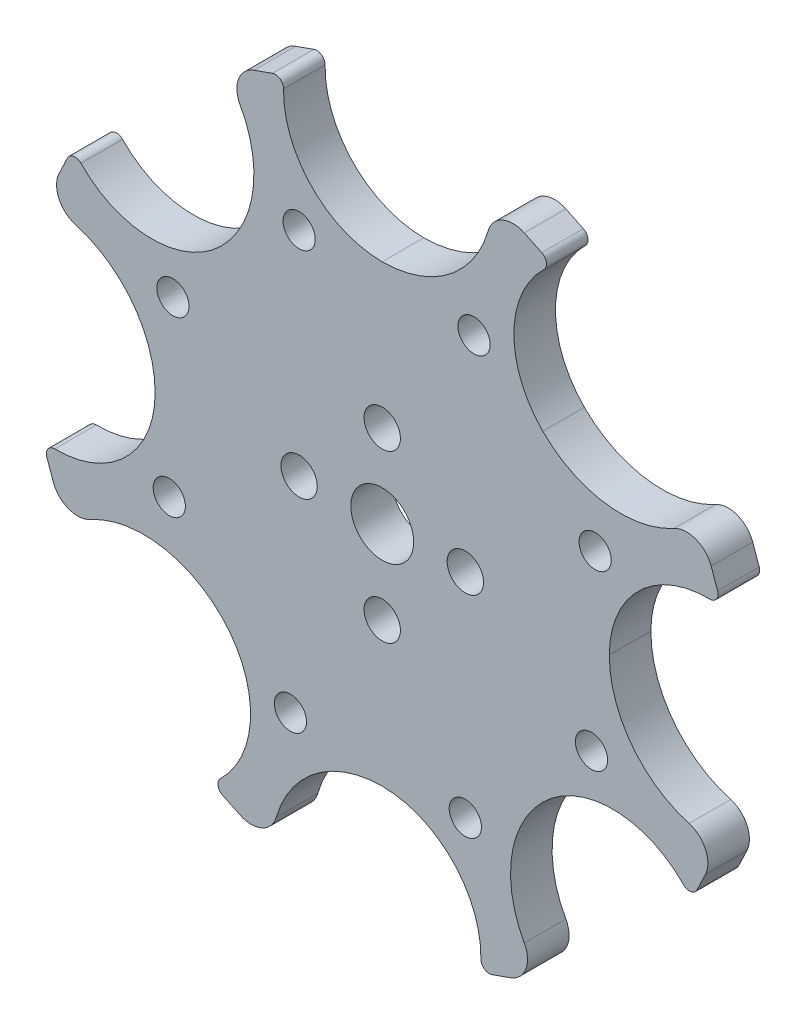
SolidWorks part; units mm, degrees
material "Thornel Mat VMA"
ref_plane "前视基准面" through (0, 0, 0) normal (0, 0, 1) x (1, 0, 0)
ref_plane "上视基准面" through (0, 0, 0) normal (0, 1, 0) x (1, 0, 0)
ref_plane "右视基准面" through (0, 0, 0) normal (1, 0, 0) x (0, 0, -1)
sketch "草图1" plane through (0, 0, 0) normal (0, 0, 1) x (1, 0, 0)
  line L0 (0, 31.3575) -> (0, 0) construction
  line L1 (0, 0) -> (22.1731, 22.1731) construction
  line L4 (0, 31.3575) -> (22.1731, 22.1731) construction
  line L6 (11.6409, 26.5357) -> (12.5976, 28.8454) construction
  line L7 (21.7656, 23.184) -> (15.5687, 29.0018) construction
  line L8 (21.7656, 23.184) -> (27.9942, 29.8184) construction
  line L9 (15.357, 30.2989) -> (13.674, 31.1018)
  line L10 (32.2836, 10.5656) -> (31.6613, 12.3233)
  line L11 (30.2989, -15.357) -> (31.1018, -13.674)
  line L12 (10.5656, -32.2836) -> (12.3233, -31.6613)
  line L13 (-15.357, -30.2989) -> (-13.674, -31.1018)
  line L14 (-32.2836, -10.5656) -> (-31.6613, -12.3233)
  line L15 (-30.2989, 15.357) -> (-31.1018, 13.674)
  line L16 (-10.5656, 32.2836) -> (-12.3233, 31.6613)
  circle A0 centre (0, 0) radius 31.3575 construction
  arc A9 (15.5687, 29.0018) -> (15.4556, 15.4556) centre (22.1731, 22.1731) ccw
  circle A13 centre (0, 0) radius 40.9 construction
  arc A16 (15.5687, 29.0018) -> (15.357, 30.2989) centre (15.0125, 29.5769) ccw
  arc A17 (13.674, 31.1018) -> (10.1948, 29.5357) centre (12.5976, 28.8454) ccw
  arc A18 (0, 21.8575) -> (10.1948, 29.5357) centre (0, 32.4647) ccw
  arc A19 (31.5161, 9.4987) -> (21.8575, 0) centre (31.3575, 0) ccw
  arc A20 (31.5161, 9.4987) -> (32.2836, 10.5656) centre (31.5295, 10.2986) ccw
  arc A21 (31.6613, 12.3233) -> (28.0937, 13.6761) centre (29.3046, 11.4889) ccw
  arc A22 (15.4556, 15.4556) -> (28.0937, 13.6761) centre (22.956, 22.956) ccw
  arc A24 (29.0018, -15.5687) -> (15.4556, -15.4556) centre (22.1731, -22.1731) ccw
  arc A25 (29.0018, -15.5687) -> (30.2989, -15.357) centre (29.5769, -15.0125) ccw
  arc A26 (31.1018, -13.674) -> (29.5357, -10.1948) centre (28.8454, -12.5976) ccw
  arc A27 (21.8575, 0) -> (29.5357, -10.1948) centre (32.4647, 0) ccw
  arc A29 (9.4987, -31.5161) -> (0, -21.8575) centre (0, -31.3575) ccw
  arc A30 (9.4987, -31.5161) -> (10.5656, -32.2836) centre (10.2986, -31.5295) ccw
  arc A31 (12.3233, -31.6613) -> (13.6761, -28.0937) centre (11.4889, -29.3046) ccw
  arc A32 (15.4556, -15.4556) -> (13.6761, -28.0937) centre (22.956, -22.956) ccw
  arc A34 (-15.5687, -29.0018) -> (-15.4556, -15.4556) centre (-22.1731, -22.1731) ccw
  arc A35 (-15.5687, -29.0018) -> (-15.357, -30.2989) centre (-15.0125, -29.5769) ccw
  arc A36 (-13.674, -31.1018) -> (-10.1948, -29.5357) centre (-12.5976, -28.8454) ccw
  arc A37 (0, -21.8575) -> (-10.1948, -29.5357) centre (0, -32.4647) ccw
  arc A39 (-31.5161, -9.4987) -> (-21.8575, 0) centre (-31.3575, 0) ccw
  arc A40 (-31.5161, -9.4987) -> (-32.2836, -10.5656) centre (-31.5295, -10.2986) ccw
  arc A41 (-31.6613, -12.3233) -> (-28.0937, -13.6761) centre (-29.3046, -11.4889) ccw
  arc A42 (-15.4556, -15.4556) -> (-28.0937, -13.6761) centre (-22.956, -22.956) ccw
  arc A44 (-29.0018, 15.5687) -> (-15.4556, 15.4556) centre (-22.1731, 22.1731) ccw
  arc A45 (-29.0018, 15.5687) -> (-30.2989, 15.357) centre (-29.5769, 15.0125) ccw
  arc A46 (-31.1018, 13.674) -> (-29.5357, 10.1948) centre (-28.8454, 12.5976) ccw
  arc A47 (-21.8575, 0) -> (-29.5357, 10.1948) centre (-32.4647, 0) ccw
  arc A49 (-9.4987, 31.5161) -> (0, 21.8575) centre (0, 31.3575) ccw
  arc A50 (-9.4987, 31.5161) -> (-10.5656, 32.2836) centre (-10.2986, 31.5295) ccw
  arc A51 (-12.3233, 31.6613) -> (-13.6761, 28.0937) centre (-11.4889, 29.3046) ccw
  arc A52 (-15.4556, 15.4556) -> (-13.6761, 28.0937) centre (-22.956, 22.956) ccw
  circle A54 centre (0, 0) radius 3.025
  circle A55 centre (0, 0) radius 8 construction
  circle A56 centre (-8, 0) radius 1.75
  circle A57 centre (0, 8) radius 1.75
  circle A58 centre (8, 0) radius 1.75
  circle A59 centre (0, -8) radius 1.75
  point P98 (0, 0)
  point P102 (0, 0)
  dimension "D1" = 9.5
  dimension "D3" = 45
  dimension "D5" = 9.1
  dimension "D8" = 81.8
  dimension "D9" = 9.5
  dimension "D10" = 2.5
  dimension "D11" = 0.8
  dimension "D13" = 6.05
  dimension "D14" = 16
  dimension "D15" = 3.5
  dimension "D2" = 24
  dimension "D6" = 11.4
  dimension "D7" = 2.5
  dimension "D17" = 8.5
  dimension "D12" = 8
  dimension "D16" = 4
extrude "凸台-拉伸1" add sketch "草图1" along normal blind 4
sketch "草图2" plane through (0, 0, 4) normal (0, 0, 1) x (1, 0, 0)
  line L1 (11.6409, 26.5357) -> (0, 0) construction
  circle A0 centre (0, 0) radius 22 construction
  circle A1 centre (8.8381, 20.1467) radius 1.55
  circle A2 centre (-8.8381, -20.1467) radius 1.55
  circle A3 centre (20.4953, 7.9964) radius 1.55
  circle A4 centre (20.1467, -8.8381) radius 1.55
  circle A5 centre (7.9964, -20.4953) radius 1.55
  circle A6 centre (-20.4953, -7.9964) radius 1.55
  circle A7 centre (-20.1467, 8.8381) radius 1.55
  circle A8 centre (-7.9964, 20.4953) radius 1.55
  point P19 (0, 0)
  dimension "D1" = 44
  dimension "D2" = 3.1
  dimension "D3" = 8
extrude "切除-拉伸1" cut sketch "草图2" against normal blind 10
